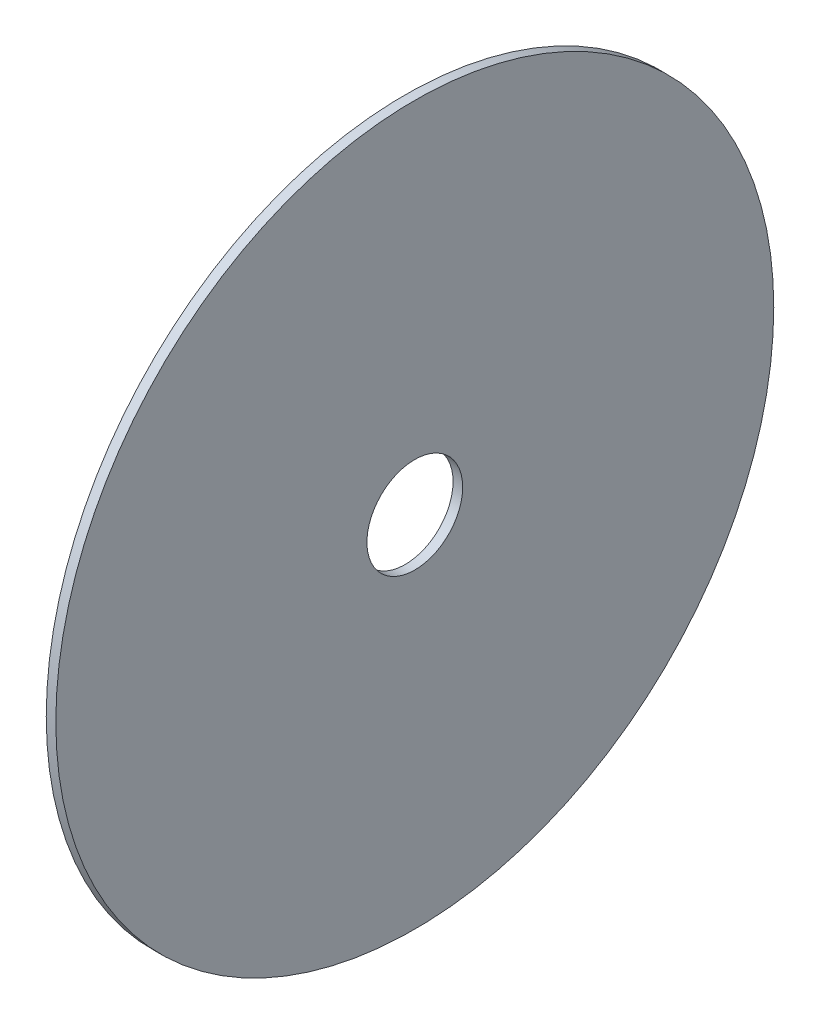
SolidWorks part; units mm, degrees
ref_plane "Спереди" through (0, 0, 0) normal (0, 0, 1) x (1, 0, 0)
ref_plane "Сверху" through (0, 0, 0) normal (0, 1, 0) x (1, 0, 0)
ref_plane "Справа" through (0, 0, 0) normal (1, 0, 0) x (0, 0, -1)
sketch "Эскиз1" plane through (0, 0, 0) normal (1, 0, 0) x (0, 0, -1)
  circle A0 centre (0, 0) radius 75
  circle A1 centre (0, 0) radius 10
extrude "Бобышка-Вытянуть1" add sketch "Эскиз1" along normal blind 2
